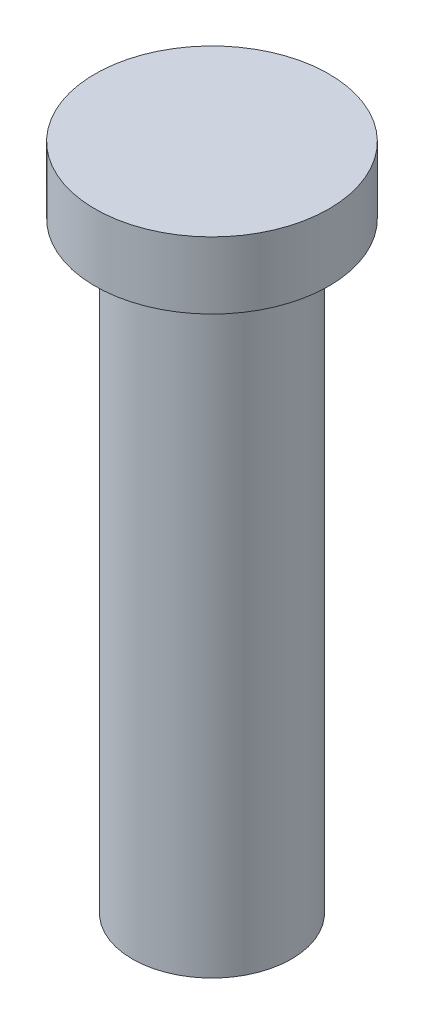
SolidWorks part; units mm, degrees
material "Plain Carbon Steel"
ref_plane "Front Plane" through (0, 0, 0) normal (0, 0, 1) x (1, 0, 0)
ref_plane "Top Plane" through (0, 0, 0) normal (0, 1, 0) x (1, 0, 0)
ref_plane "Right Plane" through (0, 0, 0) normal (1, 0, 0) x (0, 0, -1)
sketch "Sketch1" plane through (0, 0, 0) normal (0, 0, 1) x (1, 0, 0)
  line L0 (0, 0) -> (0, 40) construction
  line L1 (0, 0) -> (4.7625, 0)
  line L2 (4.7625, 0) -> (4.7625, 36)
  line L3 (4.7625, 36) -> (7, 36)
  line L4 (7, 36) -> (7, 40)
  line L5 (7, 40) -> (0, 40)
  line L6 (0, 40) -> (0, 0)
revolve "Revolve1" add sketch "Sketch1" angle 360 about L0
